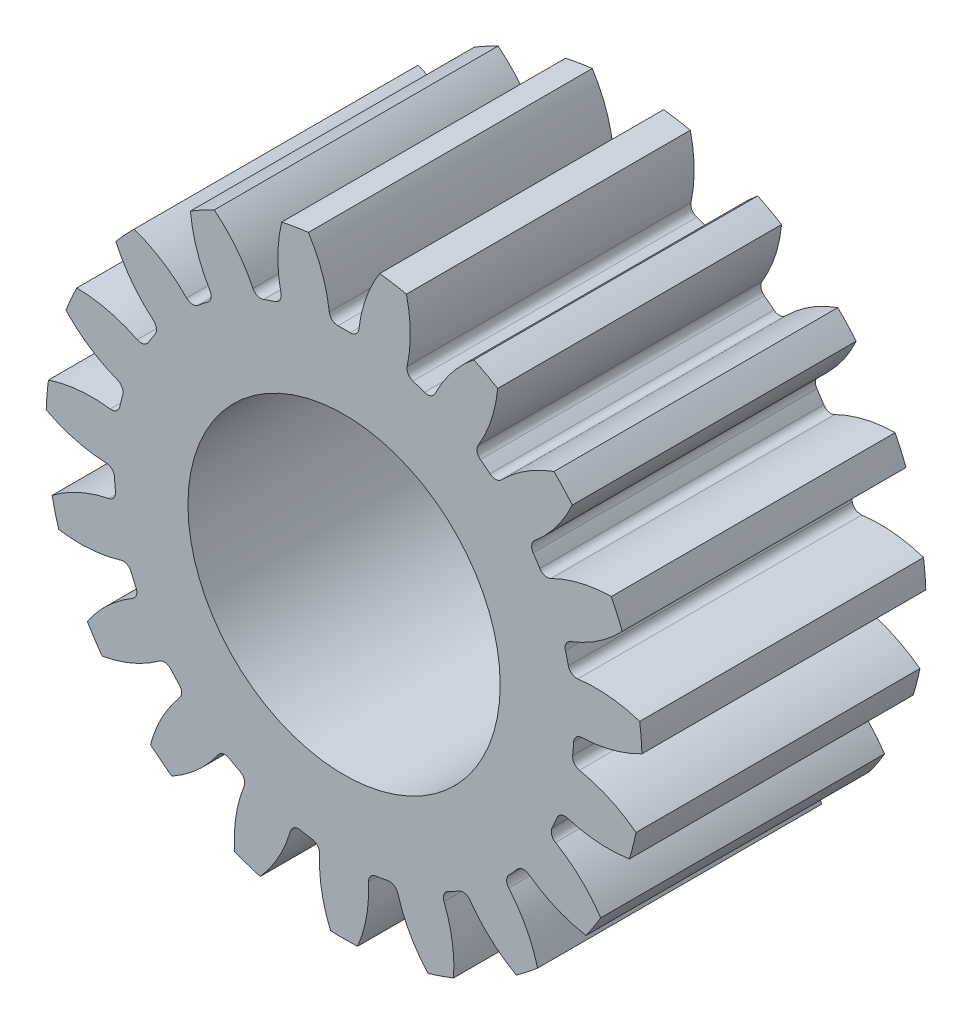
SolidWorks part; units mm, degrees
ref_plane "Front Plane" through (0, 0, 0) normal (0, 0, 1) x (1, 0, 0)
ref_plane "Top Plane" through (0, 0, 0) normal (0, 1, 0) x (1, 0, 0)
ref_plane "Right Plane" through (0, 0, 0) normal (1, 0, 0) x (0, 0, -1)
sketch "Sketch2" plane through (0, 0, 0) normal (0, 0, 1) x (1, 0, 0)
  circle A0 centre (0, 0) radius 9.5 construction
  circle A1 centre (0, 0) radius 10.5
  dimension "D1" = 19
  dimension "D2" = 21
extrude "Boss-Extrude1" add sketch "Sketch2" along normal mid plane 10 contours A1
sketch "Sketch3" plane through (0, 0, 0) normal (0, 0, 1) x (1, 0, 0)
  line L0 (0, 10.5) -> (0, 0) construction
  line L1 (0, 0) -> (3.4093, 9.9311) construction
  line L2 (0, 0) -> (1.7282, 10.3568) construction
  line L3 (-0.4967, 8.0848) -> (0, 0) construction
  line L4 (-0.7845, 9.4676) -> (0.7845, 9.4676) construction
  line L5 (0.7845, 9.4676) -> (2.3321, 9.2093) construction
  line L6 (-1.1378, 10.4382) -> (0, 7.3121) construction
  circle A0 centre (0, 0) radius 8.5 construction
  arc A1 (0.4967, 8.0848) -> (-0.4967, 8.0848) centre (0, 0) ccw
  circle A2 centre (0, 0) radius 10.5 construction
  circle A3 centre (0, 0) radius 9.5 construction
  arc A4 (-1.2558, 10.4246) -> (-0.4967, 8.0848) centre (-5.4136, 7.7827) cw
  arc A5 (1.2558, 10.4246) -> (0.4967, 8.0848) centre (5.4136, 7.7827) ccw
  arc A6 (1.2558, 10.4246) -> (-1.2558, 10.4246) centre (0, 0) ccw
  dimension "D4" = 19
  dimension "D1" = 18.947
  dimension "D3" = 2.4
  dimension "D5" = 20
extrude "Cut-Extrude1" cut sketch "Sketch3" against normal through all both and the other way through all
fillet "Fillet1" radius 0.3 2 edges at (0.4967, 8.0848, 0) (-0.4967, 8.0848, 0)
ref_axis "Axis1" through (0, 0, -11) along (0, 0, 1)
pattern_circular "CirPattern1" count 19 over 360 about axis through (0, 0, -11) along (0, 0, 1) of "Cut-Extrude1", "Fillet1"
sketch "Sketch4" plane through (0, 0, -5) normal (0, 0, -1) x (-1, 0, 0)
  circle A1 centre (0, 0) radius 5.5
  dimension "D1" = 11
extrude "Cut-Extrude3" cut sketch "Sketch4" against normal blind 10
equation "\"Module\"= 1"
equation "\"Number of teeth\"= 19"
equation "\"pressure angle\"= 20"
equation "\"D1@Sketch2\"=\"Module\"*\"Number of teeth\""
equation "\"D2@Sketch2\"=(\"Number of teeth\"+2) *\"Module\""
equation "\"D1@Sketch3\"=360 /\"Number of teeth\""
equation "\"D2@Sketch3\"=\"Module\"*2"
equation "\"D3@Sketch3\"=\"Module\" *if( \"Module\"=> 1.25,2.25,2.4)"
equation "\"D5@Sketch3\"=\"pressure angle\""
equation "\"D4@Sketch3\"=\"Module\"*\"Number of teeth\""
equation "\"D1@CirPattern1\"=\"Number of teeth\""
equation "\"D1@Fillet1\"=0.3 *\"Module\""
